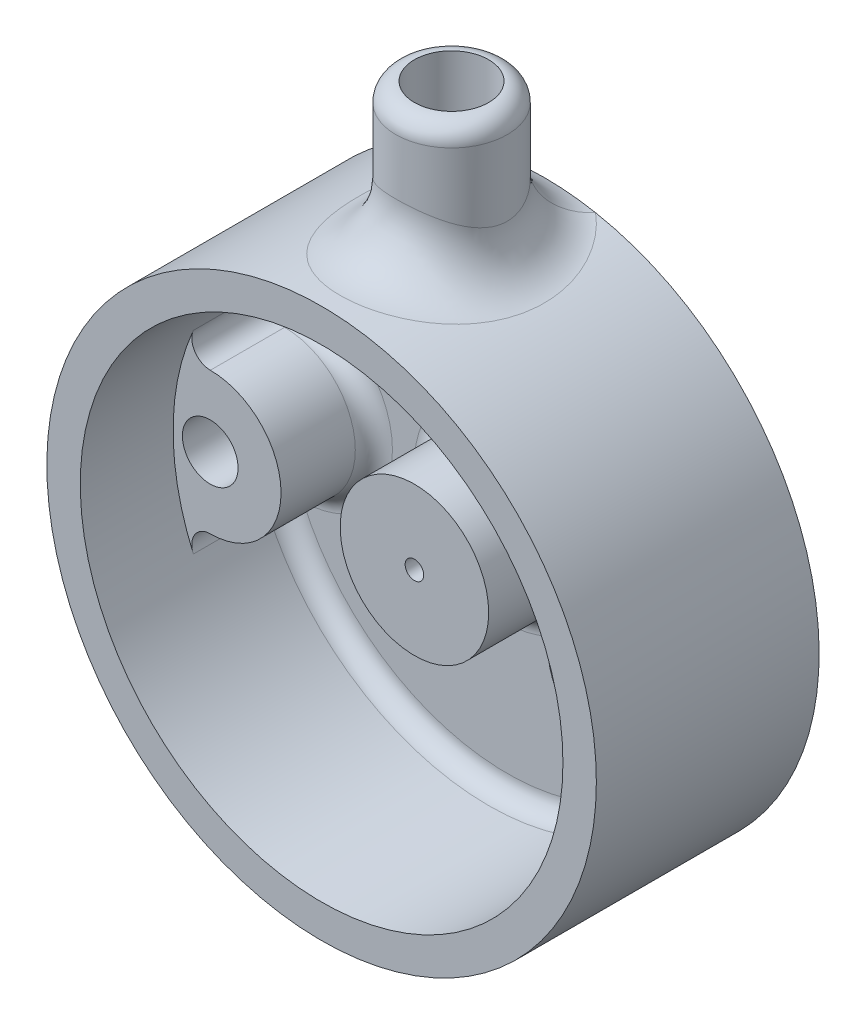
SolidWorks part; units mm, degrees
ref_plane "Plan de face" through (0, 0, 0) normal (0, 0, 1) x (1, 0, 0)
ref_plane "Plan de dessus" through (0, 0, 0) normal (0, 1, 0) x (1, 0, 0)
ref_plane "Plan de droite" through (0, 0, 0) normal (1, 0, 0) x (0, 0, -1)
sketch "Esquisse1" plane through (0, 0, 0) normal (0, 0, 1) x (1, 0, 0)
  line L0 (-11, 0) -> (11, 0) construction
  circle A0 centre (0, 0) radius 14.8
  circle A1 centre (-11, 0) radius 1.5
  circle A2 centre (11, 0) radius 1.5
  dimension "D1" = 11
extrude "Boss.-Extru.1" add sketch "Esquisse1" along normal blind 2
sketch "Esquisse2" plane through (0, 0, 2) normal (0, 0, 1) x (1, 0, 0)
  circle A0 centre (0, 0) radius 14.8
  arc A1 (-12.52, -3.5) -> (12.52, -3.5) centre (0, 0) ccw
  circle A2 centre (-11, 0) radius 1.5
  circle A3 centre (11, 0) radius 1.5
  arc A4 (-12.52, -3.5) -> (-12.52, 3.5) centre (-11, 0) ccw
  arc A5 (12.52, 3.5) -> (12.52, -3.5) centre (11, 0) ccw
  circle A6 centre (0, 0) radius 4
  arc A7 (12.52, 3.5) -> (-12.52, 3.5) centre (0, 0) ccw
  circle A11 centre (0, 0) radius 0.5
  circle M1 centre (0, 0) radius 14.8
  circle M18 centre (-11, 0) radius 1.5
  circle M19 centre (11, 0) radius 1.5
extrude "Boss.-Extru.2" add sketch "Esquisse2" along normal blind 10 contours A7 A5 A1 A4 M1 M19 M18 | A6 A11 region at (-14.3814, 0, 2) region at (-3.8869, 0, 2)
ref_plane "Plan1" through (0, 21.8, 0) normal (0, 1, 0) x (1, 0, 0)
sketch "Esquisse4" plane through (0, 21.8, 0) normal (0, 1, 0) x (1, 0, 0)
  circle A0 centre (0, -5) radius 2
  dimension "D1" = 5
extrude "Enlèv. mat.-Extru.2" cut sketch "Esquisse4" against normal up to surface (8.8 mm away) up to face at (0, 8.25, 7)
sketch "Esquisse5" plane through (0, 21.8, 0) normal (0, 1, 0) x (1, 0, 0)
  circle A0 centre (0, -5) radius 2
  circle A1 centre (0, -5) radius 3
extrude "Boss.-Extru.3" add sketch "Esquisse5" against normal up to surface (7 mm away) up to face at (0.4395, 14.7935, 3.0489)
fillet "Congé1" radius 3 1 edges at (-0.6215, 14.7869, 2.0651)
fillet "Congé2" radius 1 1 edges at (0, 21.8, 8)
fillet "Congé3" radius 1 4 edges at (12.52, -3.5, 7) (-12.52, -3.5, 7) (-12.52, 3.5, 7) (12.52, 3.5, 7)
sketch "Esquisse6" plane through (0, 0, 12) normal (0, 0, 1) x (1, 0, 0)
  circle A0 centre (0, 0) radius 13
extrude "Enlèv. mat.-Extru.3" cut sketch "Esquisse6" against normal blind 5
fillet "Congé4" radius 1 9 edges at (4, 0, 2) (-11.8288, -4.2694, 2) (-7.1842, 0, 2) (-11.8288, 4.2694, 2) (0, 13, 2) (11.8288, 4.2694, 2) (7.1842, 0, 2) (11.8288, -4.2694, 2) (0, -13, 2)
